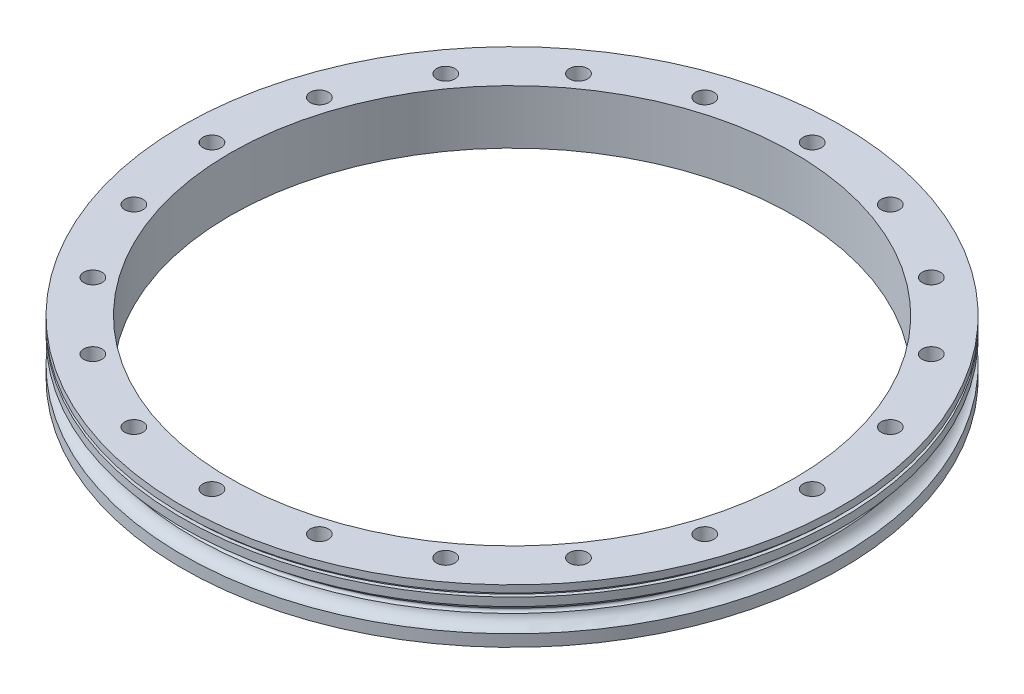
SolidWorks part; units mm, degrees
ref_plane "Plan de face" through (0, 0, 0) normal (0, 0, 1) x (1, 0, 0)
ref_plane "Plan de dessus" through (0, 0, 0) normal (0, 1, 0) x (1, 0, 0)
ref_plane "Plan de droite" through (0, 0, 0) normal (1, 0, 0) x (0, 0, -1)
sketch "Esquisse1" plane through (0, 0, 0) normal (0, 0, 1) x (1, 0, 0)
  line L0 (0, 0) -> (-335.4, 0) construction
  line L1 (-335.4, 0) -> (-335.4, 46) construction
  line L2 (-335.4, 46) -> (0, 46) construction
  line L3 (0, 46) -> (0, 0) construction
  line L4 (-335.4, 0) -> (-282, 0) construction
  line L5 (-282, 0) -> (-282, 10) construction
  line L6 (-282, 10) -> (-282, 30) construction
  line L7 (-282, 46) -> (-282, 42.7532) construction
  line L8 (-282, 46) -> (-335.4, 46) construction
  line L9 (-282, 20) -> (-291.5, 20) construction
  line L10 (-291.5, 20) -> (-293.5, 20) construction
  line L11 (-280, 46) -> (-280, 40)
  line L12 (-280, 40) -> (-277, 40)
  line L13 (-277, 40) -> (-277, 37)
  line L14 (-282, 46) -> (-282, 30) construction
  line L15 (-282, 42.7532) -> (-282, 46) construction
  line L16 (-281, 46) -> (-281, 0) construction
  line L17 (-280, 30) -> (-280, 46) construction
  line L18 (-280, 46) -> (-239.5, 46)
  line L19 (-239.5, 46) -> (-239.5, 0)
  line L20 (-239.5, 0) -> (-280, 0)
  line L21 (-277, 37) -> (-280, 37)
  line L22 (-280, 37) -> (-280, 30)
  line L23 (-280, 0) -> (-280, 10)
  line L24 (-280, 37) -> (-282, 37) construction
  line L25 (-282, 37) -> (-335.4, 37) construction
  line L26 (-335.4, 37) -> (-335.4, -9) construction
  line L27 (-282, 46) -> (-280, 46) construction
  line L28 (-335.4, -9) -> (-282, -9) construction
  line L30 (-282, 0) -> (-282, -3) construction
  line L31 (-282, -3) -> (-285, -3) construction
  line L32 (-285, -3) -> (-285, 0) construction
  line L33 (-285, 0) -> (-282, 0) construction
  line L34 (-282, 0) -> (-282, -9) construction
  arc A0 (-282, 30) -> (-282, 10) centre (-282, 20) ccw construction
  arc A1 (-291.8026, 21.977) -> (-291.8026, 18.023) centre (-291.5, 20) ccw construction
  arc A2 (-291.8026, 18.023) -> (-282, 10) centre (-282, 20) ccw construction
  arc A3 (-282, 30) -> (-291.8026, 21.977) centre (-282, 20) ccw construction
  arc A4 (-270.1974, 21.977) -> (-270.1974, 18.023) centre (-270.5, 20) cw
  arc A5 (-280, 30) -> (-280, 10) centre (-280, 20) cw construction
  arc A6 (-280, 30) -> (-270.1974, 21.977) centre (-280, 20) cw
  arc A7 (-270.1974, 18.023) -> (-280, 10) centre (-280, 20) cw
  dimension "D7" = 10
  dimension "D8" = 9.5
  dimension "D9" = 2
  dimension "D2" = 3
  dimension "D3" = 20
  dimension "D4" = 3
  dimension "D5" = 560
  dimension "D6" = 46
  dimension "D10" = 9
  dimension "D11" = 1
  dimension "D12" = 3
  dimension "D13" = 3
  dimension "D14" = 46
  dimension "D15" = 479
  dimension "D17" = 335.4
revolve "Révolution1" add sketch "Esquisse1" angle 360 about L3
sketch "Esquisse4" plane through (0, 46, 0) normal (0, 1, 0) x (1, 0, 0)
  line L0 (0, 0) -> (-255, 0) construction
  circle A0 centre (-255, 0) radius 7.75
  point P38 (0, 0)
  dimension "D1" = 15.5
  dimension "D2" = 255
extrude "Enlèv. mat.-Extru.2" cut sketch "Esquisse4" against normal through all
ref_axis "Axe2" through (0, 45.15, 0) along (0, -1, 0)
pattern_circular "Répétition circulaire1" count 20 over 360 about axis through (0, 45.15, 0) along (0, -1, 0) of "Enlèv. mat.-Extru.2"
